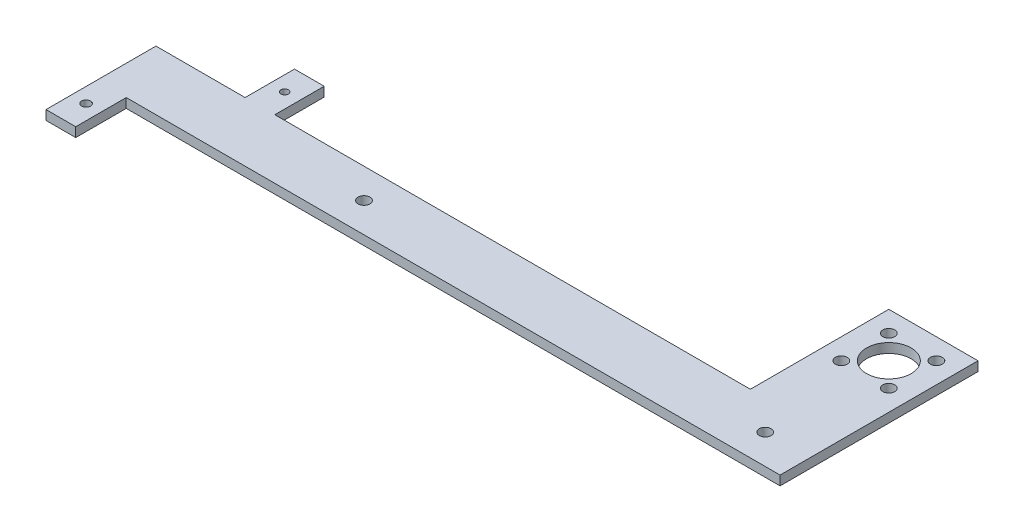
SolidWorks part; units mm, degrees
ref_plane "Front" through (0, 0, 0) normal (0, 0, 1) x (1, 0, 0)
ref_plane "Top" through (0, 0, 0) normal (0, 1, 0) x (1, 0, 0)
ref_plane "Right" through (0, 0, 0) normal (1, 0, 0) x (0, 0, -1)
sketch "Sketch1" plane through (0, 0, 0) normal (0, 1, 0) x (1, 0, 0)
  line L0 (190, -36.6) -> (190, 0)
  line L3 (0, -36.6) -> (190, -36.6)
  line L5 (190, -26.6) -> (0, -26.6)
  line L6 (190, -26.6) -> (175, -26.6)
  line L7 (175, -26.6) -> (40, -26.6)
  line L8 (0, -16.6) -> (160, -16.6)
  line L9 (160, 3.4) -> (160, -16.6)
  line L10 (190, 0) -> (190, 30)
  line L11 (190, 30) -> (160, 30)
  line L12 (160, 30) -> (160, 3.4)
  line L13 (0, -16.6) -> (0, 0)
  line L14 (175, 15) -> (175, 23)
  line L15 (175, 23) -> (183, 23)
  line L16 (183, 23) -> (183, 7)
  line L17 (183, 7) -> (167, 7)
  line L18 (167, 7) -> (167, 23)
  line L19 (167, 23) -> (175, 23)
  line L20 (0, -36.6) -> (-10, -36.6)
  line L21 (-10, 0) -> (-10, -16.6)
  line L22 (-10, 0) -> (0, 0)
  line L23 (0, -16.6) -> (-10, 0)
  line L24 (-10, -16.6) -> (-40, -16.6)
  line L25 (-40, -16.6) -> (-40, -53.6)
  line L26 (-40, -53.6) -> (-30, -53.6)
  line L27 (-30, -53.6) -> (-30, -36.6)
  line L28 (-30, -36.6) -> (-10, -36.6)
  line L29 (-30, -36.6) -> (-40, -53.6)
  circle A0 centre (40, -26.6) radius 2
  circle A1 centre (175, -26.6) radius 2
  circle A2 centre (183, 7) radius 2
  circle A3 centre (167, 7) radius 2
  circle A4 centre (183, 23) radius 2
  circle A5 centre (167, 23) radius 2
  circle A6 centre (175, 15) radius 7.5
  circle A7 centre (-5, -8.3) radius 1.25
  circle A9 centre (-35, -45.1) radius 1.5
  dimension "D5" = 160
  dimension "D11" = 10
  dimension "D12" = 30
  dimension "D15" = 15
  dimension "D2" = 190
  dimension "D3" = 15
  dimension "D4" = 135
  dimension "D6" = 30
  dimension "D7" = 8
  dimension "D8" = 8
  dimension "D9" = 8
  dimension "D10" = 16
  dimension "D13" = 37
  dimension "D14" = 10
  dimension "D16" = 20
  dimension "D17" = 16.6
extrude "Boss-Extrude1" add sketch "Sketch1" along normal blind 3.175 contours A9 L29 L26 L27 | A9 L29 L28 L20 L3 L0 A1 A0 L10 L11 L12 L9 L8 L23 A7 L21 L24 L25 A5 L19 L15 A4 L16 A2 L17 A3 L18 | A7 L23 L13 L22 | A6 L19 A5 L18 A3 L17 A2 L16 A4 L15 region at (91.0809, 0, 20.7257) region at (-33.2848, 0, 48.0423) region at (-3.2964, 0, 5.4574) region at (178, 0, -22.7737)
